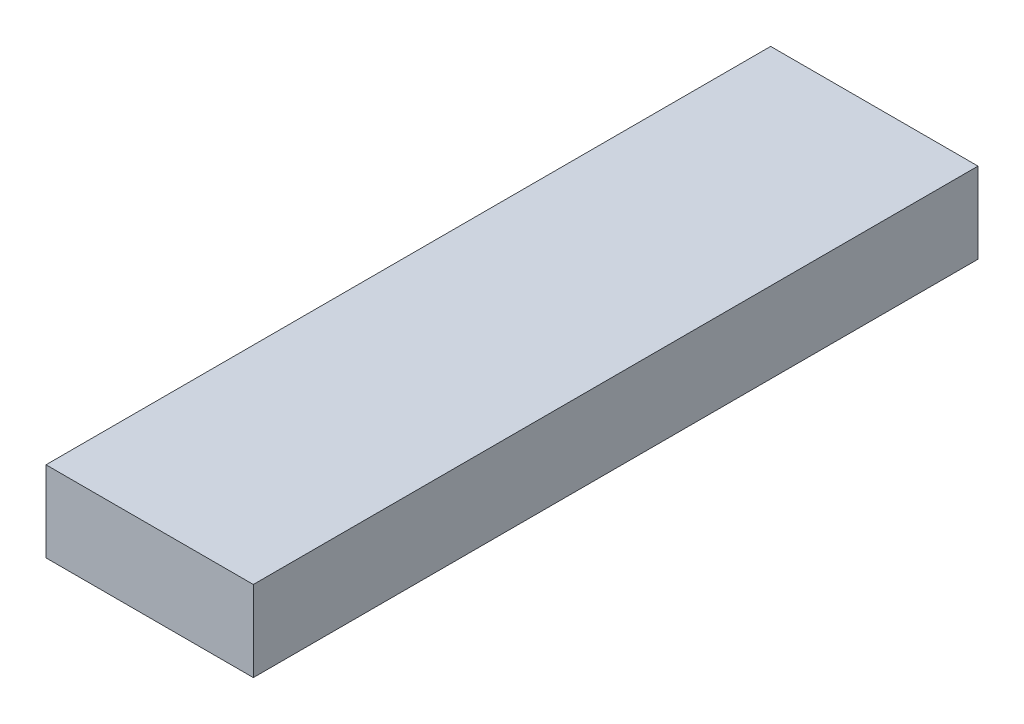
SolidWorks part; units mm, degrees
ref_plane "Front Plane" through (0, 0, 0) normal (0, 0, 1) x (1, 0, 0)
ref_plane "Top Plane" through (0, 0, 0) normal (0, 1, 0) x (1, 0, 0)
ref_plane "Right Plane" through (0, 0, 0) normal (1, 0, 0) x (0, 0, -1)
sketch "Sketch1" plane through (0, 0, 0) normal (0, 0, 1) x (1, 0, 0)
  line L1 (0, 0) -> (72.6741, 0)
  line L2 (0, 0) -> (0, 28.2712)
  line L3 (0, 28.2712) -> (72.6741, 28.2712)
  line L4 (72.6741, 0) -> (72.6741, 28.2712)
extrude "Boss-Extrude1" add sketch "Sketch1" along normal blind 254
